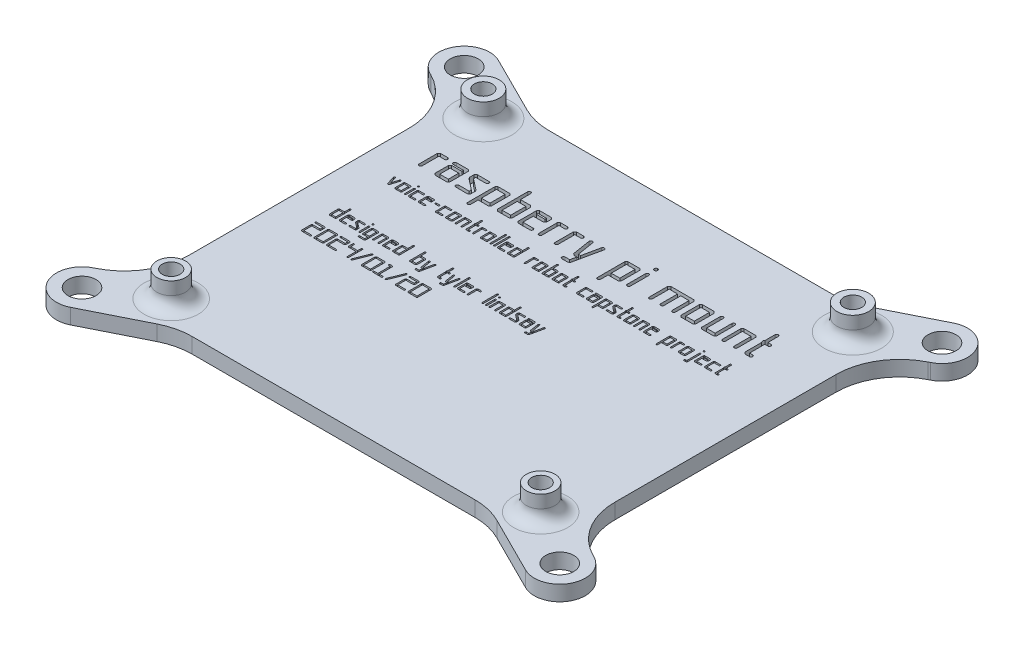
SolidWorks part; units mm, degrees
ref_plane "Front Plane" through (0, 0, 0) normal (0, 0, 1) x (1, 0, 0)
ref_plane "Top Plane" through (0, 0, 0) normal (0, 1, 0) x (1, 0, 0)
ref_plane "Right Plane" through (0, 0, 0) normal (1, 0, 0) x (0, 0, -1)
sketch "Sketch2" plane through (0, 0, 0) normal (0, 1, 0) x (1, 0, 0)
  line L1 (-33.5, -28) -> (33.5, -28)
  line L2 (-33.5, -28) -> (-33.5, 28)
  line L3 (-33.5, 28) -> (33.5, 28)
  line L4 (33.5, -28) -> (33.5, 28)
  line L5 (-33.5, -28) -> (33.5, 28) construction
  line L6 (-33.5, 28) -> (33.5, -28) construction
  point P0 (0, 0)
  dimension "D1" = 56
  dimension "D2" = 67
extrude "Boss-Extrude1" add sketch "Sketch2" along normal blind 2.4
sketch "Sketch3" plane through (0, 0, 0) normal (0, 1, 0) x (1, 0, 0)
  line L0 (-29, 24.5) -> (-29, -24.5) construction
  line L1 (-33.5, 28) -> (-33.5, -28) construction
  circle A0 centre (-29, 24.5) radius 2.5
  circle A1 centre (-29, -24.5) radius 2.25
  circle A2 centre (29, 24.5) radius 2.5
  circle A3 centre (29, -24.5) radius 2.25
  point P6 (-33.5, 0)
  point P7 (-29, 0)
  dimension "D1" = 5
  dimension "D2" = 4.5
  dimension "D3" = 49
  dimension "D4" = 2
  dimension "D5" = 4.5
extrude "Boss-Extrude2" add sketch "Sketch3" along normal blind 4 from surface starting at face at (0, 2.4, 0)
sketch "Sketch4" plane through (0, 0, 0) normal (0, 1, 0) x (1, 0, 0)
  circle A0 centre (-29, 24.5) radius 1.4
  circle A1 centre (29, 24.5) radius 1.4
  circle A2 centre (-29, -24.5) radius 1.4
  circle A3 centre (29, -24.5) radius 1.4
  dimension "D1" = 2.8
  dimension "D2" = 2.8
  dimension "D3" = 2.8
  dimension "D4" = 2.8
extrude "Cut-Extrude1" cut sketch "Sketch4" along normal through all
sketch "Sketch5" plane through (0, 0, 0) normal (0, 1, 0) x (1, 0, 0)
  line L0 (0, 28) -> (0, -28) construction
  line L1 (33.5, 28) -> (-33.5, 28) construction
  line L2 (-33.5, -28) -> (33.5, -28) construction
  line L3 (-37.5, 30) -> (37.5, 30)
  line L4 (-33.5, 28) -> (-37.5, 30)
  line L5 (-33.5, 23.5279) -> (-39.2889, 26.4223)
  line L6 (33.5, 28) -> (-33.5, 28)
  line L7 (-24.5557, 28) -> (-35.7111, 33.5777)
  line L8 (-33.5, 28) -> (-33.5, -28) construction
  line L9 (-33.5, 28) -> (-33.5, -28)
  circle A0 centre (-37.5, 30) radius 2.2
  arc A2 (-35.7111, 33.5777) -> (-39.2889, 26.4223) centre (-37.5, 30) ccw
  point P13 (0, 30)
  dimension "D2" = 4.4
  dimension "D4" = 8
  dimension "D1" = 75
  dimension "D6" = 2
extrude "Boss-Extrude3" add sketch "Sketch5" along normal up to surface (2.4 mm away) contours L7 A2 L5 L9 L4 A0 L3 | A0 L4 L6 L7 L3 region at (-39.8032, 0, -30.5437) region at (-30.6894, 0, -28.9554) up to face at (29, 2.4, 22.25)
mirror "Mirror1" about plane through (0, 0, 0) normal (1, 0, 0) of "Boss-Extrude3"
mirror "Mirror2" about plane through (0, 0, 0) normal (0, 0, 1) of "Mirror1"
fillet "Fillet1" radius 2 4 edges at (-29, 2.4, 22.25) (29, 2.4, 22.25) (29, 2.4, -27) (-29, 2.4, -27)
sketch "Sketch6" plane through (0, 2.4, 0) normal (0, 1, 0) x (1, 0, 0)
  line L0 (24.5557, 28) -> (-24.5557, 28) construction
  text T0 "raspberry pi mount" font "Lover" height 5
  text T1 "voice-controlled robot capstone project\r\n\r\ndesigned by tyler lindsay\r\n2024/01/20" font "Lover" height 2.4
  dimension "D1" = 5
  dimension "D2" = 15
extrude "Cut-Extrude2" cut sketch "Sketch6" against normal blind 1 from surface starting at face at (-29, 2.4, 20.25)
fillet "Fillet3" radius 10 8 edges at (-24.5557, 1.2, 28) (24.5557, 1.2, 28) (33.5, 1.2, -23.5279) (33.5, 1.2, 23.5279) (-24.5557, 1.2, -28) (24.5557, 1.2, -28) (-33.5, 1.2, 23.5279) (-33.5, 1.2, -23.5279)
